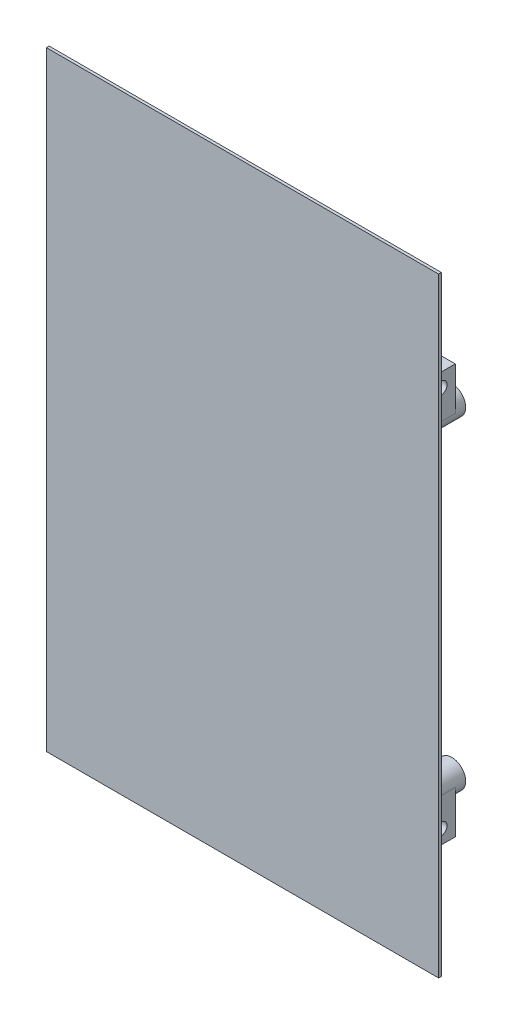
SolidWorks part; units mm, degrees
ref_plane "Front Plane" through (0, 0, 0) normal (0, 0, 1) x (1, 0, 0)
ref_plane "Top Plane" through (0, 0, 0) normal (0, 1, 0) x (1, 0, 0)
ref_plane "Right Plane" through (0, 0, 0) normal (1, 0, 0) x (0, 0, -1)
sketch "Sketch1" plane through (0, 0, 0) normal (0, 0, 1) x (1, 0, 0)
  line L1 (109, 161.3091) -> (-4, 161.3091)
  line L2 (109, 161.3091) -> (109, -14.3091)
  line L3 (109, -14.3091) -> (-4, -14.3091)
  line L4 (-4, 161.3091) -> (-4, -14.3091)
extrude "Boss-Extrude1" add sketch "Sketch1" along normal blind 0.8
sketch "Sketch2" plane through (0, 0, 0) normal (0, 0, -1) x (-1, 0, 0)
  circle A0 centre (-7.2, 26.85) radius 2 construction
  circle A1 centre (-101, 26.85) radius 2 construction
  circle A2 centre (-101, 120.15) radius 2 construction
  circle A3 centre (-7.2, 120.15) radius 2 construction
  circle A4 centre (-7.2, 26.85) radius 2
  circle A5 centre (-101, 26.85) radius 2
  circle A6 centre (-101, 120.15) radius 2
  circle A7 centre (-7.2, 120.15) radius 2
  circle A8 centre (-7.2, 120.15) radius 4
  circle A9 centre (-7.2, 26.85) radius 4
  circle A10 centre (-101, 26.85) radius 4
  circle A11 centre (-101, 120.15) radius 4
  dimension "D1" = 8
extrude "Boss-Extrude2" add sketch "Sketch2" along normal up to surface (11 mm away)
sketch "Sketch3" plane through (0, 0, 0) normal (0, 0, -1) x (-1, 0, 0)
  line L0 (-101, 120.15) -> (-7.2, 120.15) construction
  line L1 (-8.9321, 123.15) -> (-9.8458, 123.15)
  line L2 (-10.6641, 120.15) -> (-8.9321, 117.15)
  line L3 (-8.9321, 117.15) -> (-5.4679, 117.15)
  line L4 (-5.4679, 117.15) -> (-3.7359, 120.15)
  line L5 (-3.7359, 120.15) -> (-5.4679, 123.15)
  line L6 (-5.4679, 123.15) -> (-8.9321, 123.15)
  line L7 (-8.9321, 123.15) -> (-10.6641, 120.15)
  line L8 (-8.9321, 117.15) -> (-9.8458, 117.15)
  line L9 (-52.5, 161.3091) -> (-52.5, -14.3091) construction
  line L10 (-109, 161.3091) -> (4, 161.3091) construction
  line L11 (4, -14.3091) -> (-109, -14.3091) construction
  line L12 (-99.2679, 123.15) -> (-98.3542, 123.15)
  line L13 (-97.5359, 120.15) -> (-99.2679, 123.15)
  line L14 (-99.2679, 123.15) -> (-102.7321, 123.15)
  line L15 (-102.7321, 123.15) -> (-104.4641, 120.15)
  line L16 (-104.4641, 120.15) -> (-102.7321, 117.15)
  line L17 (-102.7321, 117.15) -> (-99.2679, 117.15)
  line L18 (-99.2679, 117.15) -> (-97.5359, 120.15)
  line L19 (-97.5359, 26.85) -> (-99.2679, 29.85)
  line L20 (-109, 73.5) -> (4, 73.5) construction
  line L21 (-109, -14.3091) -> (-109, 161.3091) construction
  line L22 (4, 161.3091) -> (4, -14.3091) construction
  line L23 (-8.9321, 29.85) -> (-9.8458, 29.85)
  line L24 (-8.9321, 29.85) -> (-5.4679, 29.85)
  line L25 (-10.6641, 26.85) -> (-8.9321, 29.85)
  line L26 (-3.7359, 26.85) -> (-5.4679, 23.85)
  line L27 (-5.4679, 29.85) -> (-3.7359, 26.85)
  line L28 (-8.9321, 23.85) -> (-10.6641, 26.85)
  line L29 (-5.4679, 23.85) -> (-8.9321, 23.85)
  line L30 (-8.9321, 23.85) -> (-9.8458, 23.85)
  line L31 (-99.2679, 29.85) -> (-102.7321, 29.85)
  line L32 (-102.7321, 29.85) -> (-104.4641, 26.85)
  line L33 (-104.4641, 26.85) -> (-102.7321, 23.85)
  line L34 (-102.7321, 23.85) -> (-99.2679, 23.85)
  line L35 (-99.2679, 23.85) -> (-97.5359, 26.85)
  line L36 (-99.2679, 117.15) -> (-98.3542, 117.15)
  line L37 (-99.2679, 29.85) -> (-98.3542, 29.85)
  line L38 (-99.2679, 23.85) -> (-98.3542, 23.85)
  circle A0 centre (-7.2, 120.15) radius 3 construction
  circle A1 centre (-7.2, 120.15) radius 4 construction
  circle A2 centre (-7.2, 120.15) radius 4 construction
  circle A3 centre (-101, 120.15) radius 3 construction
  circle A4 centre (-101, 26.85) radius 3 construction
  circle A5 centre (-101, 26.85) radius 4 construction
  circle A6 centre (-101, 120.15) radius 4 construction
  circle A7 centre (-101, 26.85) radius 4
  circle A8 centre (-101, 120.15) radius 4
  circle M15 centre (-101, 120.15) radius 4
  circle M16 centre (-101, 26.85) radius 4
  circle M17 centre (-7.2, 26.85) radius 4
  circle M18 centre (-7.2, 120.15) radius 4
  dimension "D1" = 6
extrude "Cut-Extrude1" cut sketch "Sketch3" along normal blind 3.5 contours L6 L7 L2 L3 L4 L5 | L8 L2 L7 L1 M18 | L17 L18 L13 L14 L15 L16 | L18 L36 L12 L13 M15 | L35 L38 L37 L19 M16 | L34 L35 L19 L31 L32 L33 | L29 L26 L27 L24 L25 L28 | L30 L28 L25 L23 M17 region at (9.8536, 121.6821, 0) region at (7.2, 120.15, 0) region at (98.8111, 123.0859, 0) region at (101, 120.15, 0) region at (101, 26.85, 0) region at (98.3464, 28.3821, 0) region at (9.8536, 28.3821, 0) region at (7.2, 26.85, 0)
sketch "Sketch4" plane through (0, 0, 0) normal (0, 0, -1) x (-1, 0, 0)
  line L0 (-105, -14.3091) -> (-105, 161.3091) construction
  line L1 (-105, 14.5) -> (-100, 14.5)
  line L2 (-105, 14.5) -> (-105, 22.5)
  line L3 (-105, 22.5) -> (-100, 22.5)
  line L4 (-100, 14.5) -> (-100, 22.5)
  line L5 (-100, 18.5) -> (-105, 18.5) construction
  line L6 (-105, 26.85) -> (-105, 22.5)
  line L7 (-101, 120.15) -> (-101, 26.85) construction
  line L8 (-100, 22.5) -> (-100, 22.977)
  line L9 (-109, 73.5) -> (4, 73.5) construction
  line L10 (-109, -14.3091) -> (-109, 161.3091) construction
  line L11 (4, 161.3091) -> (4, -14.3091) construction
  line L12 (-105, 120.15) -> (-105, 124.5)
  line L13 (-105, 132.5) -> (-105, 124.5)
  line L14 (-105, 132.5) -> (-100, 132.5)
  line L15 (-109, 18.5) -> (-105, 18.5) construction
  line L16 (-105, 124.5) -> (-100, 124.5)
  line L17 (-100, 132.5) -> (-100, 124.5)
  line L18 (-100, 124.5) -> (-100, 124.023)
  line L19 (-52.5, 161.3091) -> (-52.5, -14.3091) construction
  line L20 (-109, 161.3091) -> (4, 161.3091) construction
  line L21 (4, -14.3091) -> (-109, -14.3091) construction
  line L22 (-105, 161.3091) -> (-105, -14.3091) construction
  line L23 (0, 161.3091) -> (0, -14.3091) construction
  line L24 (0, 14.5) -> (-5, 14.5)
  line L25 (0, 22.5) -> (-5, 22.5)
  line L26 (0, 14.5) -> (0, 22.5)
  line L27 (0, 132.5) -> (0, 124.5)
  line L28 (0, 124.5) -> (-5, 124.5)
  line L29 (0, 132.5) -> (-5, 132.5)
  line L30 (-5, 132.5) -> (-5, 124.5)
  line L31 (-3.2, 120.15) -> (-3.2, 124.5)
  line L32 (-5, 124.5) -> (-5, 123.4907)
  line L33 (-5, 14.5) -> (-5, 23.5093)
  line L34 (-3.2, 26.85) -> (-3.2, 22.5)
  arc A0 (-98.3542, 29.85) -> (-98.3542, 23.85) centre (-101, 26.85) ccw construction
  arc A1 (-9.8458, 117.15) -> (-9.8458, 123.15) centre (-7.2, 120.15) ccw construction
  arc A2 (-98.3542, 29.85) -> (-98.3542, 23.85) centre (-101, 26.85) ccw construction
  circle A3 centre (-7.2, 120.15) radius 4 construction
  arc A4 (-9.8458, 23.85) -> (-9.8458, 29.85) centre (-7.2, 26.85) ccw construction
  point P26 (-101, 73.5)
  arc M5 (-98.3542, 117.15) -> (-98.3542, 123.15) centre (-101, 120.15) cw
  arc M10 (-98.3542, 23.85) -> (-98.3542, 29.85) centre (-101, 26.85) cw
  arc M15 (-9.8458, 29.85) -> (-9.8458, 23.85) centre (-7.2, 26.85) cw
  arc M20 (-9.8458, 123.15) -> (-9.8458, 117.15) centre (-7.2, 120.15) cw
  dimension "D1" = 8
  dimension "D2" = 5
extrude "Boss-Extrude3" add sketch "Sketch4" along normal blind 8 contours L1 L4 L3 L2 | L3 L8 M10 | L18 L16 L12 M5 | L17 L14 L13 L16 | L28 L32 L31 M20 | L29 L30 L28 L27 | L33 L24 L26 L25 | L34 L33 L25 M15 region at (102.5, 18.5, 0) region at (103.5375, 23.3788, 0) region at (103.5375, 123.6212, 0) region at (102.5, 128.5, 0) region at (2.5, 18.5, 0) region at (3.907, 23.6469, 0) region at (2.5, 128.5, 0) region at (3.907, 123.3531, 0)
sketch "Sketch5" plane through (105, 0, 0) normal (-1, 0, 0) x (0, 0, 1)
  line L0 (-4, 120.15) -> (-4, 26.85) construction
  line L1 (-8, 120.15) -> (0, 120.15) construction
  line L2 (-8, 26.85) -> (0, 26.85) construction
  line L3 (-4, 73.5) -> (0, 73.5) construction
  line L4 (0, -14.3091) -> (0, 161.3091) construction
  circle A0 centre (-3.8964, 128.5) radius 1.75
  circle A1 centre (-3.8964, 18.5) radius 1.75
  circle A2 centre (-3.8964, 18.5) radius 2.9 construction
  dimension "D1" = 3.5
extrude "Cut-Extrude2" cut sketch "Sketch5" along normal up to surface (105 mm away) up to face at (0, 18.5, -4)
sketch "Sketch6" plane through (100, 0, 0) normal (-1, 0, 0) x (0, 0, 1)
  line L0 (-4, 120.15) -> (-4, 26.85) construction
  line L1 (-3.8964, 21.9641) -> (-6.8964, 20.2321)
  line L2 (-6.8964, 20.2321) -> (-6.8964, 16.7679)
  line L3 (-6.8964, 16.7679) -> (-3.8964, 15.0359)
  line L4 (-3.8964, 15.0359) -> (-0.8964, 16.7679)
  line L5 (-0.8964, 16.7679) -> (-0.8964, 20.2321)
  line L6 (-0.8964, 20.2321) -> (-3.8964, 21.9641)
  line L7 (-8, 120.15) -> (0, 120.15) construction
  line L8 (-8, 26.85) -> (0, 26.85) construction
  line L9 (-4, 73.5) -> (0, 73.5) construction
  line L10 (0, -14.3091) -> (0, 161.3091) construction
  line L11 (-0.8964, 130.2321) -> (-0.8964, 126.7679)
  line L12 (-0.8964, 126.7679) -> (-3.8964, 125.0359)
  line L13 (-3.8964, 125.0359) -> (-6.8964, 126.7679)
  line L14 (-6.8964, 126.7679) -> (-6.8964, 130.2321)
  line L15 (-6.8964, 130.2321) -> (-3.8964, 131.9641)
  line L16 (-3.8964, 131.9641) -> (-0.8964, 130.2321)
  circle A0 centre (-3.8964, 18.5) radius 3 construction
  dimension "D1" = 6
extrude "Cut-Extrude3" cut sketch "Sketch6" against normal blind 2.5
sketch "Sketch7" plane through (0, 0, 0) normal (0, 0, -1) x (-1, 0, 0)
  line L0 (-109, 73.5) -> (4, 73.5) construction
  line L1 (-109, -14.3091) -> (-109, 161.3091) construction
  line L2 (4, 161.3091) -> (4, -14.3091) construction
  line L3 (-52.5, -14.3091) -> (-52.5, 161.3091) construction
  line L4 (0, -14.3091) -> (-105, -14.3091) construction
  line L5 (0, 161.3091) -> (-105, 161.3091) construction
  line L6 (-109, -14.3091) -> (4, 161.3091) construction
  line L7 (4, -14.3091) -> (-109, 161.3091) construction
  line L8 (-91.1065, 13.5) -> (-13.8935, 13.5) construction
  line L9 (-91.1065, 133.5) -> (-13.8935, 133.5) construction
  line L10 (-91.1065, 13.5) -> (-91.1065, 133.5) construction
  line L11 (-13.8935, 13.5) -> (-13.8935, 133.5) construction
  line L12 (-93.6065, 11) -> (-11.3935, 11)
  line L13 (-11.3935, 11) -> (-11.3935, 136)
  line L14 (-93.6065, 136) -> (-11.3935, 136)
  line L15 (-93.6065, 11) -> (-93.6065, 136)
  line L16 (-109, 71) -> (4, 71)
  line L17 (6.1024, -12.9563) -> (-106.8976, 162.6619)
  line L18 (-50, -14.3091) -> (-50, 161.3091)
  line L19 (-106.8976, -15.6619) -> (6.1024, 159.9563)
  line L20 (-88.6065, 16) -> (-16.3935, 16)
  line L21 (-16.3935, 16) -> (-16.3935, 131)
  line L22 (-88.6065, 131) -> (-16.3935, 131)
  line L23 (-88.6065, 16) -> (-88.6065, 131)
  line L24 (-109, 76) -> (4, 76)
  line L25 (1.8976, -15.6619) -> (-111.1024, 159.9563)
  line L26 (-55, -14.3091) -> (-55, 161.3091)
  line L27 (-111.1024, -12.9563) -> (1.8976, 162.6619)
  dimension "D1" = 60
  dimension "D2" = 2.5
  dimension "D3" = 2.5
extrude "Boss-Extrude4" [suppressed] add sketch "Sketch7" along normal blind 0.5 contours L12 L26 L20 L19 | L27 L15 L12 L19 L20 L23 | L15 L27 L23 L16 | L27 L23 L20 L19 L26 L16 | L24 L15 L16 L23 | L16 L27 L25 L24 L23 | L23 L25 L15 L24 | L25 L23 L22 L17 L14 L15 | L24 L26 L17 L22 L23 L25 | L22 L26 L14 L17 | L26 L22 L18 L14 | L17 L27 L18 L22 L26 | L22 L27 L14 L18 | L27 L22 L21 L19 L13 L14 | L27 L18 L24 L19 L21 L22 | L21 L24 L13 L19 | L24 L21 L16 L13 | L24 L19 L17 L16 L21 | L21 L17 L13 L16 | L25 L20 L21 L17 L16 L18 | L26 L20 L18 L25 L19 | L26 L12 L18 L20 | L12 L25 L20 L18 | L25 L12 L13 L17 L21 L20 | L26 L19 L25 L16 | L27 L16 L26 L25 | L26 L16 L25 | L25 L27 L26 L24 | L27 L25 L26 | L26 L27 L24 | L24 L27 L17 L26 | L27 L17 L24 L18 | L24 L18 L17 L19 | L19 L18 L16 L17 | L19 L16 L18 | L25 L18 L16 L19 | L25 L19 L16 | L27 L26 L25 L16 L19 L18 L17 L24 | L27 L24 L17 | L24 L17 L18 | L18 L19 L17
ref_plane "Plane7" through (52.5, 0, 0) normal (-1, 0, 0) x (0, 0, 1)
mirror "Mirror1" about plane through (52.5, 0, 0) normal (-1, 0, 0) of "Cut-Extrude3"
